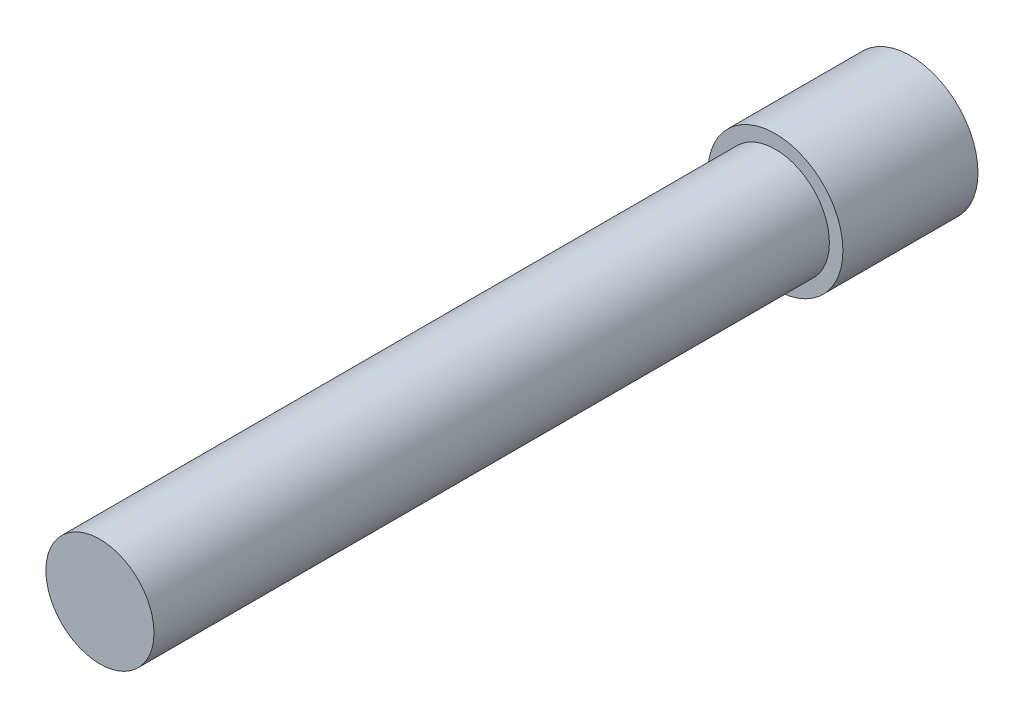
SolidWorks part; units mm, degrees
ref_plane "前视基准面" through (0, 0, 0) normal (0, 0, 1) x (1, 0, 0)
ref_plane "上视基准面" through (0, 0, 0) normal (0, 1, 0) x (1, 0, 0)
ref_plane "右视基准面" through (0, 0, 0) normal (1, 0, 0) x (0, 0, -1)
other "Configuration Table"
sketch "Sketch1" plane through (0, 0, 0) normal (0, 1, 0) x (1, 0, 0)
  line L0 (0, 0) -> (4, 0)
  line L1 (4, 0) -> (4, 50)
  line L2 (4, 50) -> (5, 50)
  line L3 (5, 50) -> (5, 60)
  line L4 (5, 60) -> (0, 60)
  line L5 (0, 60) -> (0, 0)
  line L6 (0, 0) -> (0, 60) construction
revolve "Revolve1" add sketch "Sketch1" angle 360 about L6
sketch3d "3DSketch1"
  line L0 (0, 0, 0) -> (0, 0, -60) construction
ref_axis "screw_axis" through (0, 0, 0) along (0, 0, -1)
ref_plane "head_bottom_face" through (0, 0, -50) normal (0, 0, 1) x (1, 0, 0)
